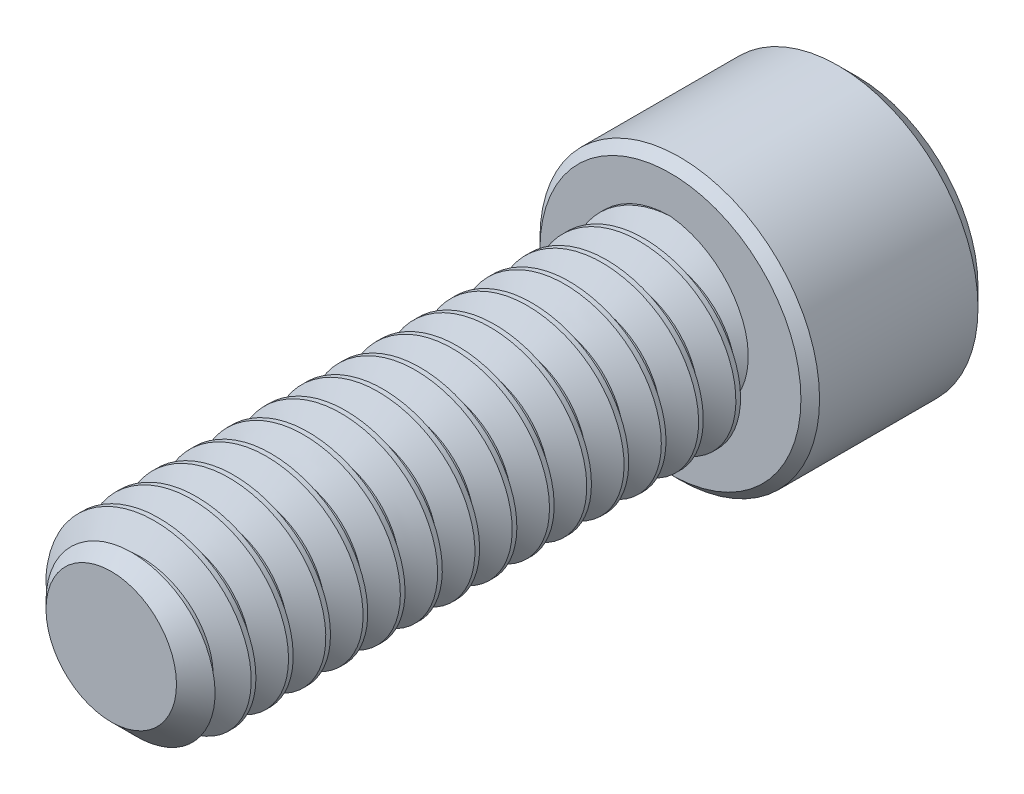
SolidWorks part; units mm, degrees
material "Plain Carbon Steel"
ref_plane "Front Plane" through (0, 0, 0) normal (0, 0, 1) x (1, 0, 0)
ref_plane "Top Plane" through (0, 0, 0) normal (0, 1, 0) x (1, 0, 0)
ref_plane "Right Plane" through (0, 0, 0) normal (1, 0, 0) x (0, 0, -1)
sketch "Sketch1" plane through (0, 0, 0) normal (0, 0, 1) x (1, 0, 0)
  line L0 (0, 3.175) -> (0, -3.175) construction
  circle A0 centre (0, 0) radius 3.175
  dimension "OD" = 6.35
extrude "Extrude1" add sketch "Sketch1" against normal blind 19.05
sketch "Sketch2" plane through (0, 0, 0) normal (0, 0, 1) x (1, 0, 0)
  circle A0 centre (0, 0) radius 3.175 construction
  circle A1 centre (0, 0) radius 3.175
curve "Helix/Spiral1" pitch 1.27 height 20.32 turns 16 parameters "pitch"=1.27
chamfer "Chamfer3" distance 0.9525 angle 45 1 edges at (3.175, 0, 0)
sketch "Sketch3" plane through (0, 0, 0) normal (1, 0, 0) x (0, 0, -1)
  line L0 (-1.1113, 3.175) -> (-0.635, 2.3501)
  line L1 (-0.635, 2.3501) -> (-0.4763, 2.3501)
  line L2 (-0.4763, 2.3501) -> (0, 3.175)
  line L3 (-1.1113, 3.175) -> (0, 3.175)
  line L4 (-0.5556, 3.175) -> (-0.5556, 2.3501) construction
  line L5 (-0.8731, 2.7626) -> (-0.2381, 2.7626) construction
  line L6 (0, 3.175) -> (0, -3.175) construction
  dimension "D1" = 0.1588
  dimension "D2" = 0.635
  dimension "D3" = 60
sweep "Cut-Sweep1" cut profiles "Sketch3" path "Helix/Spiral1"
sketch "Sketch6" plane through (0, 0, -19.05) normal (0, 0, -1) x (-1, 0, 0)
  circle A0 centre (0, 0) radius 4.7625
  dimension "head dia" = 9.525
extrude "Extrude2" add sketch "Sketch6" along normal blind 6.35
sketch "Sketch7" plane through (0, 0, -25.4) normal (0, 0, -1) x (-1, 0, 0)
  line L1 (0, 2.7496) -> (-2.3812, 1.3748)
  line L2 (-2.3812, 1.3748) -> (-2.3812, -1.3748)
  line L3 (-2.3812, -1.3748) -> (0, -2.7496)
  line L4 (0, -2.7496) -> (2.3812, -1.3748)
  line L5 (2.3812, -1.3748) -> (2.3812, 1.3748)
  line L6 (2.3812, 1.3748) -> (0, 2.7496)
  circle A0 centre (0, 0) radius 2.3813 construction
  dimension "hex dia" = 4.7625
extrude "Cut-Extrude1" cut sketch "Sketch7" against normal blind 3.5719
sketch "Sketch8" plane through (0, 0, -25.4) normal (0, 0, -1) x (-1, 0, 0)
  circle A0 centre (0, 0) radius 2.7496
extrude "Cut-Extrude2" cut sketch "Sketch8" against normal blind 0.635 draft 45
chamfer "Chamfer1" distance 0.635 angle 45 1 edges at (-4.7625, 0, -25.4)
chamfer "Chamfer2" distance 0.3175 angle 45 1 edges at (-4.7625, 0, -19.05)
sketch "Sketch9" plane through (0, 0, 0) normal (1, 0, 0) x (0, 0, -1)
  line L0 (0, 3.175) -> (0, -3.175) construction
  line L1 (6.985, 3.175) -> (6.985, -3.175) construction
  line L2 (19.05, 4.7625) -> (19.05, -4.7625) construction
  line L3 (25.4, 4.7625) -> (25.4, -4.7625) construction
  line L4 (25.4, 0) -> (0, 0) construction
  dimension "D1" = 6.985
  dimension "D2" = 6.35
  dimension "D3" = 9.525
  dimension "D4" = 19.05
equation "\"D3@Helix/Spiral1\" = \"screw length@Extrude1\"+\"pitch@Helix/Spiral1\""
equation "\"D1@Sketch3\" = \"pitch@Helix/Spiral1\"*.125"
equation "\"D2@Sketch3\" = \"pitch@Helix/Spiral1\"*.5"
equation "\"D1@Cut-Extrude1\" = \"hex dia@Sketch7\"*.75"
equation "\"D1@Chamfer1\" = \"head depth@Extrude2\"/10"
equation "\"D1@Sketch9\" = \"pitch@Helix/Spiral1\"*5.5"
equation "\"D1@Chamfer2\" = \"D1@Chamfer1\"/2"
equation "\"D1@Cut-Extrude2\" = \"D1@Chamfer2\"*2"
equation "\"D1@Chamfer3\" = \"pitch@Helix/Spiral1\"*.750"
equation "\"D2@Sketch9\" = \"head depth@Extrude2\""
equation "\"D3@Sketch9\" = \"head dia@Sketch6\""
equation "\"D4@Sketch9\" = \"screw length@Extrude1\""
